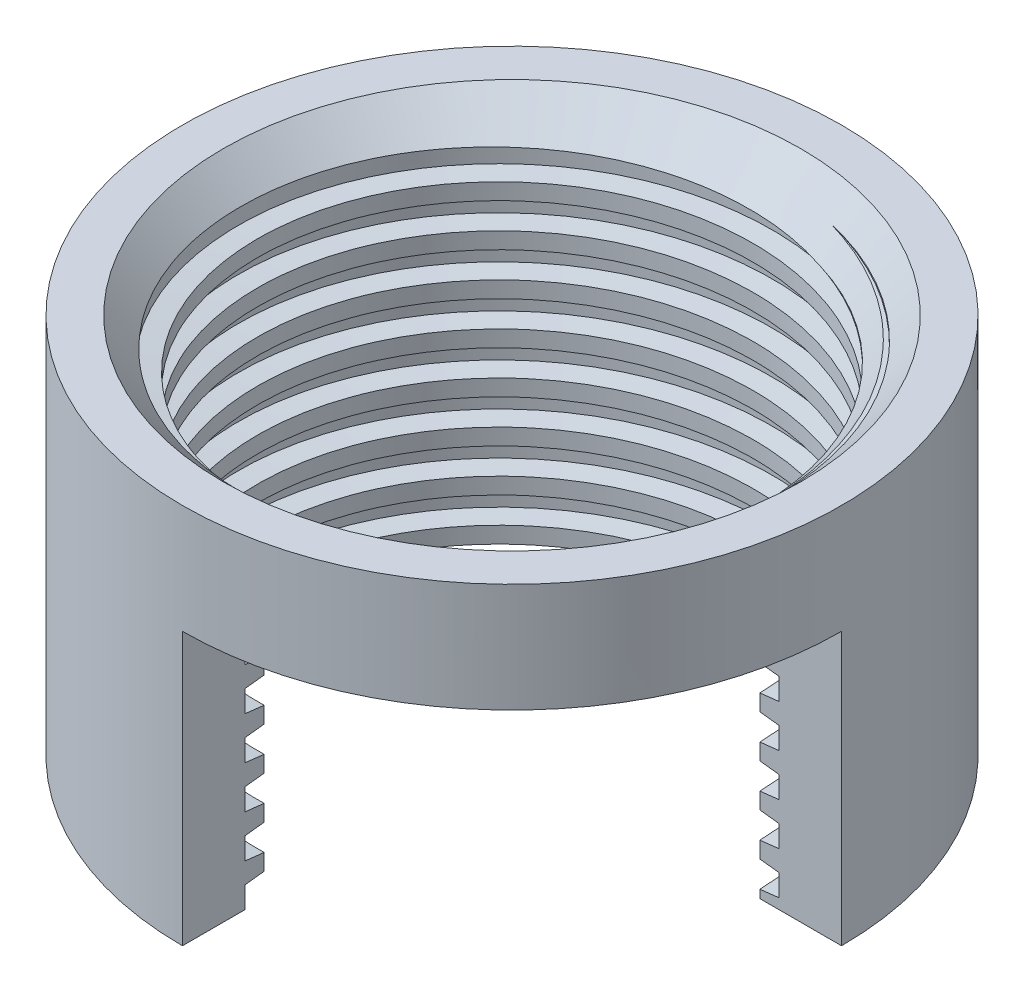
SolidWorks part; units mm, degrees
ref_plane "Front Plane" through (0, 0, 0) normal (0, 0, 1) x (1, 0, 0)
ref_plane "Top Plane" through (0, 0, 0) normal (0, 1, 0) x (1, 0, 0)
ref_plane "Right Plane" through (0, 0, 0) normal (1, 0, 0) x (0, 0, -1)
sketch "Sketch2" plane through (0, 0, 0) normal (0, 1, 0) x (1, 0, 0)
  circle A0 centre (0, 0) radius 4.55
  circle A1 centre (0, 0) radius 6.05
  dimension "D1" = 9.1
  dimension "D2" = 1.5
extrude "Boss-Extrude1" add sketch "Sketch2" along normal blind 7
sketch "Sketch3" plane through (0, 0, 0) normal (0, 0, 1) x (1, 0, 0)
  line L0 (-4.55, 0) -> (-4.9, 0) construction
  line L1 (-4.55, 0) -> (4.55, 0) construction
  line L2 (-4.9, -0.2) -> (-4.9, 0.2)
  line L3 (-4.9, 0.2) -> (-4.55, 0.24)
  line L4 (-4.55, 0.24) -> (-4.55, -0.24)
  line L5 (-4.9, -0.2) -> (-4.55, -0.24)
  dimension "D1" = 4.9
  dimension "D2" = 0.4
  dimension "D3" = 0.48
sketch "Sketch5" plane through (0, 0, 0) normal (0, 1, 0) x (1, 0, 0)
  circle A0 centre (0, 0) radius 4.55 construction
  circle A1 centre (0, 0) radius 4.55
curve "Helix/Spiral1" pitch 0.78 height 7 radius 4.55 centre (0, 0, 0) axis (0, 1, 0) start towards (0, 0, 1)
sweep "Cut-Sweep1" cut profiles "Sketch3" path "Helix/Spiral1" align with end faces yes
sketch "Sketch6" plane through (0, 0, 0) normal (0, 1, 0) x (1, 0, 0)
  line L0 (0, 0) -> (7, 0)
  line L1 (0, 0) -> (0, -7)
  arc A0 (7, 0) -> (0, -7) centre (0, 0) cw
  dimension "D1" = 7
extrude "cutout" cut sketch "Sketch6" along normal blind 5
sketch "Sketch7" plane through (0, 0, 0) normal (0, 0, 1) x (1, 0, 0)
  line L0 (6.05, 7) -> (4.55, 7) construction
  line L1 (6.05, 7) -> (-6.05, 7) construction
  line L2 (4.55, 7) -> (0.927, 7) construction
  line L3 (4.55, 7) -> (4.55, 6.25)
  line L4 (5.3, 7) -> (4.55, 6.25)
  line L5 (5.3, 7) -> (4.55, 7)
  point P7 (0, 0)
  dimension "D1" = 1.5
  dimension "D2" = 0.75
ref_axis "Axis1" through (0, 7.8074, 0) along (0, -1, 0)
revolve "Cut-Revolve1" cut sketch "Sketch7" angle 360 about axis through (0, 7.8074, 0) along (0, -1, 0)
equation "\"D2@Sketch7\"=\"D1@Sketch7\"/2"
